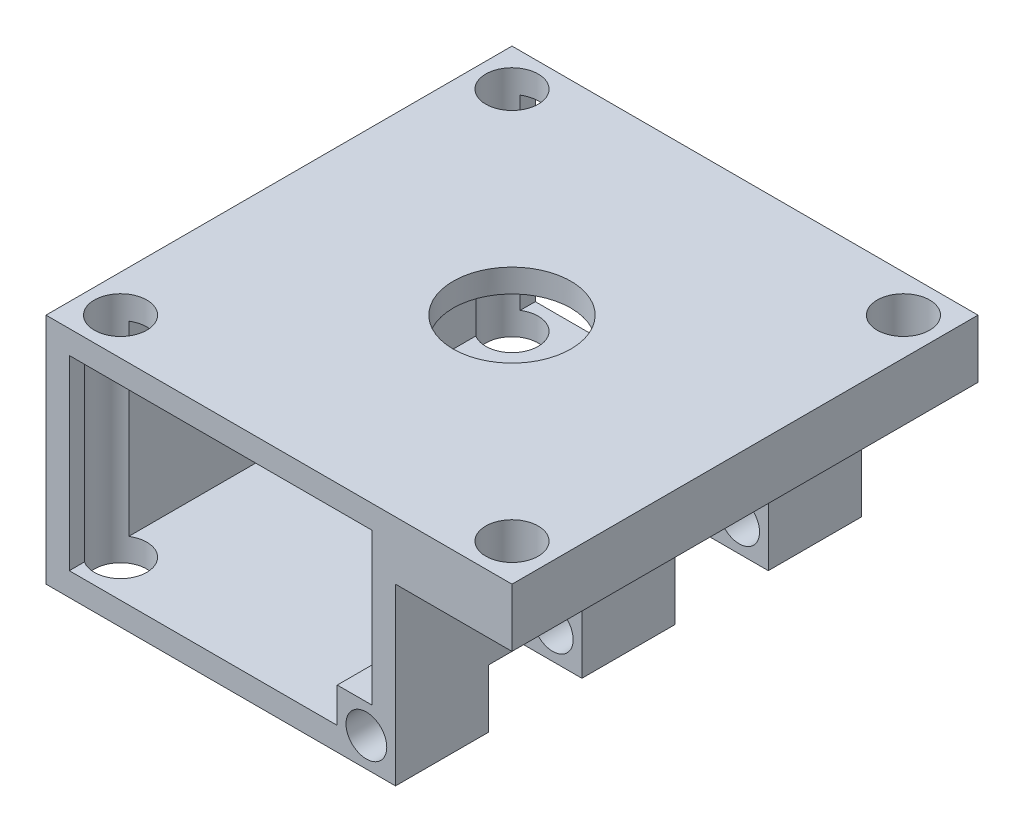
SolidWorks part; units mm, degrees
ref_plane "Front Plane" through (0, 0, 0) normal (0, 0, 1) x (1, 0, 0)
ref_plane "Top Plane" through (0, 0, 0) normal (0, 1, 0) x (1, 0, 0)
ref_plane "Right Plane" through (0, 0, 0) normal (1, 0, 0) x (0, 0, -1)
sketch "Sketch2" plane through (0, 0, 0) normal (0, 1, 0) x (1, 0, 0)
  line L1 (0, 0) -> (38.1, 0)
  line L2 (0, 0) -> (0, 50.8)
  line L3 (0, 50.8) -> (38.1, 50.8)
  line L4 (38.1, 0) -> (38.1, 50.8)
  dimension "D1" = 50.8
  dimension "D2" = 38.1
extrude "Boss-Extrude1" add sketch "Sketch2" along normal blind 25.4
shell "Shell1" thickness 2.54 removed face at (19.05, 12.7, -50.8) removed face at (19.05, 12.7, 0)
sketch "Sketch3" plane through (38.1, 0, 0) normal (1, 0, 0) x (0, 0, -1)
  line L0 (50.8, 25.4) -> (50.8, 0) construction
  line L1 (0, 25.4) -> (50.8, 25.4)
  line L2 (0, 25.4) -> (0, 19.05)
  line L3 (0, 19.05) -> (50.8, 19.05)
  line L4 (50.8, 25.4) -> (50.8, 19.05)
  dimension "D1" = 6.35
extrude "Boss-Extrude2" add sketch "Sketch3" along normal blind 12.7
sketch "Sketch4" plane through (0, 25.4, 0) normal (0, 1, 0) x (1, 0, 0)
  line L0 (0, 50.8) -> (0, 0) construction
  line L1 (50.8, 50.8) -> (0, 50.8) construction
  circle A0 centre (25.4, 25.4) radius 6.4135
  circle A1 centre (4.064, 46.736) radius 2.8575
  circle A2 centre (46.736, 46.736) radius 2.8575
  circle A3 centre (46.736, 4.064) radius 2.8575
  circle A4 centre (4.064, 4.064) radius 2.8575
  dimension "D3" = 12.827
  dimension "D4" = 5.715
  dimension "D1" = 25.4
  dimension "D2" = 25.4
  dimension "D5" = 4.064
  dimension "D6" = 4.064
  dimension "D7" = 4
extrude "Cut-Extrude1" cut sketch "Sketch4" against normal through all
sketch "Sketch5" plane through (0, 0, 0) normal (0, 0, 1) x (1, 0, 0)
  line L9 (38.1, 0) -> (31.75, 0)
  line L10 (38.1, 0) -> (38.1, 6.35)
  line L11 (38.1, 6.35) -> (31.75, 6.35)
  line L12 (31.75, 0) -> (31.75, 6.35)
  dimension "D1" = 6.35
extrude "Boss-Extrude3" add sketch "Sketch5" against normal up to surface (50.8 mm away) up to face at (29.6333, 14.8167, -50.8)
sketch "Sketch6" plane through (0, 0, 0) normal (0, 0, 1) x (1, 0, 0)
  line L0 (35.56, 6.35) -> (31.75, 6.35) construction
  line L1 (31.75, 6.35) -> (38.1, 6.35) construction
  line L2 (31.75, 6.35) -> (31.75, 0) construction
  line L3 (31.75, 0) -> (38.1, 0) construction
  line L4 (38.1, 6.35) -> (38.1, 0) construction
  line L5 (31.75, 6.35) -> (38.1, 0) construction
  line L6 (31.75, 0) -> (38.1, 6.35) construction
  line L7 (31.75, 6.35) -> (31.75, 2.54) construction
  circle A0 centre (34.925, 3.175) radius 2.2225
  dimension "D1" = 4.445
extrude "Cut-Extrude2" cut sketch "Sketch6" against normal through all
sketch "Sketch7" plane through (38.1, 0, 0) normal (1, 0, 0) x (0, 0, -1)
  line L1 (10.16, 0) -> (20.32, 0)
  line L2 (10.16, 0) -> (10.16, 6.35)
  line L3 (10.16, 6.35) -> (20.32, 6.35)
  line L4 (20.32, 0) -> (20.32, 6.35)
  line L16 (30.48, 0) -> (40.64, 0)
  line L17 (30.48, 0) -> (30.48, 6.35)
  line L18 (30.48, 6.35) -> (40.64, 6.35)
  line L19 (40.64, 0) -> (40.64, 6.35)
  line L20 (0, 0) -> (50.8, 0) construction
  line L23 (0, 19.05) -> (0, 0) construction
  dimension "D1" = 6.35
  dimension "D2" = 10.16
  dimension "D4" = 10.16
  dimension "D3" = 6.35
  dimension "D5" = 10.16
  dimension "D6" = 10.16
extrude "Cut-Extrude3" cut sketch "Sketch7" against normal blind 6.35
